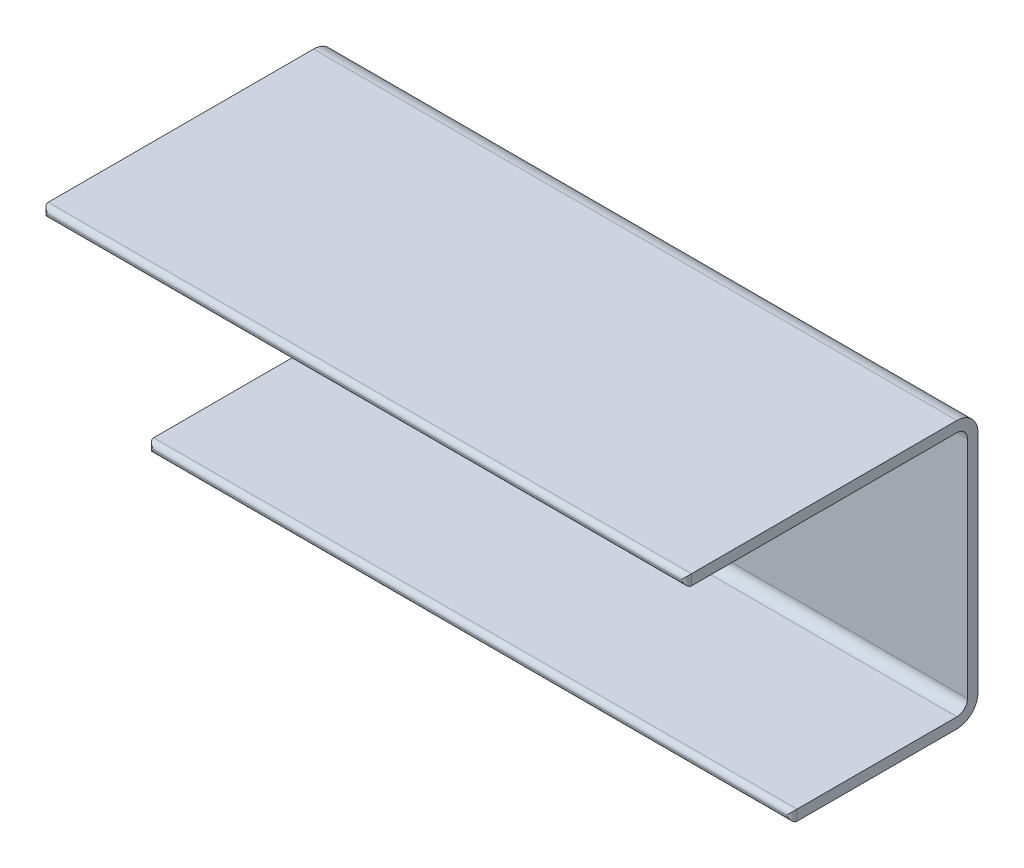
SolidWorks part; units mm, degrees
ref_plane "Front Plane" through (0, 0, 0) normal (0, 0, 1) x (1, 0, 0)
ref_plane "Top Plane" through (0, 0, 0) normal (0, 1, 0) x (1, 0, 0)
ref_plane "Right Plane" through (0, 0, 0) normal (1, 0, 0) x (0, 0, -1)
sketch "Sketch1" plane through (0, 0, 0) normal (0, 1, 0) x (1, 0, 0)
  line L1 (-91.5, -25) -> (91.5, -25)
  line L2 (-91.5, -25) -> (-91.5, 25)
  line L3 (-91.5, 25) -> (91.5, 25)
  line L4 (91.5, -25) -> (91.5, 25)
  line L5 (-91.5, -25) -> (91.5, 25) construction
  line L6 (-91.5, 25) -> (91.5, -25) construction
  point P0 (0, 0)
  dimension "D1" = 183
  dimension "D2" = 50
extrude "Boss-Extrude1" add sketch "Sketch1" along normal blind 3
sketch "Sketch2" plane through (0, 0, -25) normal (0, 0, -1) x (-1, 0, 0)
  line L0 (91.5, 3) -> (91.5, 0) construction
  line L1 (-91.5, 0) -> (91.5, 0)
  line L2 (-91.5, 0) -> (-91.5, 76)
  line L3 (-91.5, 76) -> (91.5, 76)
  line L4 (91.5, 0) -> (91.5, 76)
  dimension "D1" = 76
extrude "Boss-Extrude2" add sketch "Sketch2" along normal blind 3
sketch "Sketch3" plane through (0, 0, -25) normal (0, 0, 1) x (1, 0, 0)
  line L0 (91.5, 76) -> (91.5, 3) construction
  line L1 (-91.5, 76) -> (91.5, 76)
  line L2 (-91.5, 76) -> (-91.5, 73)
  line L3 (-91.5, 73) -> (91.5, 73)
  line L4 (91.5, 76) -> (91.5, 73)
  dimension "D1" = 3
extrude "Boss-Extrude3" add sketch "Sketch3" along normal blind 80
fillet "Fillet2" radius 1.5 8 edges at (-91.5, 1.5, 25) (0, 3, 25) (91.5, 1.5, 25) (0, 0, 25) (0, 76, 55) (91.5, 74.5, 55) (0, 73, 55) (-91.5, 74.5, 55)
sketch "Sketch4" plane through (0, 0, -25) normal (0, 0, 1) x (1, 0, 0)
  line L0 (-91.5, 45.5) -> (91.5, 45.5) construction
  line L1 (-91.5, 3) -> (-91.5, 73) construction
  line L2 (91.5, 73) -> (91.5, 3) construction
  line L3 (-14, 45.5) -> (14, 45.5) construction
  line L4 (-14, 56.5) -> (14, 56.5)
  line L5 (-14, 34.5) -> (14, 34.5)
  line L6 (-91.5, 76) -> (91.5, 76) construction
  arc A0 (-14, 56.5) -> (-14, 34.5) centre (-14, 45.5) ccw
  arc A1 (14, 34.5) -> (14, 56.5) centre (14, 45.5) ccw
  point P8 (0, 45.5)
  dimension "D2" = 11
  dimension "D1" = 28
  dimension "D3" = 30.5
extrude "Cut-Extrude1" cut sketch "Sketch4" against normal up to next
fillet "Fillet3" radius 3 2 edges at (0, 73, -25) (0, 3, -25)
fillet "Fillet4" radius 6 2 edges at (0, 76, -28) (0, 0, -28)
